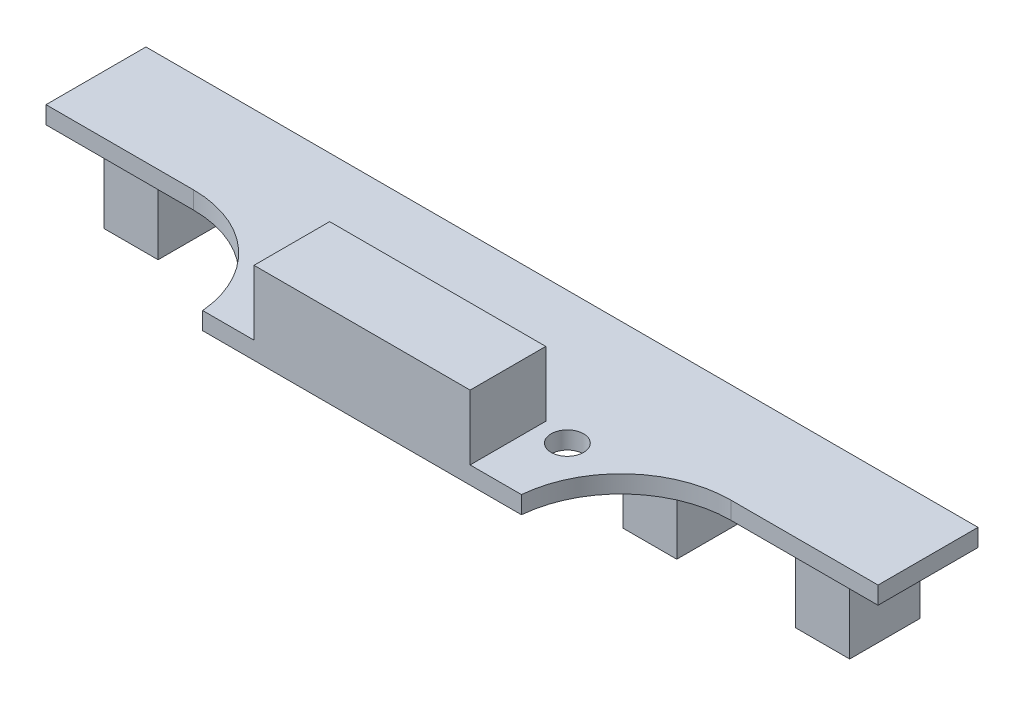
SolidWorks part; units mm, degrees
ref_plane "Front Plane" through (0, 0, 0) normal (0, 0, 1) x (1, 0, 0)
ref_plane "Top Plane" through (0, 0, 0) normal (0, 1, 0) x (1, 0, 0)
ref_plane "Right Plane" through (0, 0, 0) normal (1, 0, 0) x (0, 0, -1)
sketch "Sketch1" plane through (0, 0, 0) normal (0, 1, 0) x (1, 0, 0)
  line L0 (13.5, 12.5) -> (13.5, 6)
  line L1 (-14.75, -4.625) -> (14.75, -4.625)
  line L2 (-14.75, -4.625) -> (-14.75, 4.625)
  line L3 (-14.75, 4.625) -> (14.75, 4.625)
  line L4 (14.75, -4.625) -> (14.75, 4.625)
  line L5 (-14.75, -4.625) -> (14.75, 4.625) construction
  line L6 (-14.75, 4.625) -> (14.75, -4.625) construction
  line L7 (38.5, 4.625) -> (-38.5, 4.625)
  line L8 (38.5, 4.625) -> (38.5, 13.875)
  line L9 (38.5, 13.875) -> (-38.5, 13.875)
  line L10 (-38.5, 4.625) -> (-38.5, 13.875)
  line L11 (-2.5, 12.5) -> (2.5, 12.5)
  line L12 (-2.5, 12.5) -> (-2.5, 6)
  line L13 (-2.5, 6) -> (2.5, 6)
  line L14 (2.5, 12.5) -> (2.5, 6)
  line L15 (-2.5, 12.5) -> (2.5, 6) construction
  line L16 (-2.5, 6) -> (2.5, 12.5) construction
  line L17 (13.5, 6) -> (18.5, 6)
  line L18 (18.5, 12.5) -> (18.5, 6)
  line L19 (13.5, 12.5) -> (18.5, 12.5)
  line L20 (29.5, 12.5) -> (29.5, 6)
  line L21 (29.5, 6) -> (34.5, 6)
  line L22 (34.5, 12.5) -> (34.5, 6)
  line L23 (29.5, 12.5) -> (34.5, 12.5)
  line L24 (-2.5, 12.5) -> (13.5, 12.5) construction
  line L25 (-18.5, 12.5) -> (-18.5, 6)
  line L26 (-18.5, 12.5) -> (-13.5, 12.5)
  line L27 (-13.5, 12.5) -> (-13.5, 6)
  line L28 (-18.5, 6) -> (-13.5, 6)
  line L29 (-34.5, 12.5) -> (-34.5, 6)
  line L30 (-34.5, 12.5) -> (-29.5, 12.5)
  line L31 (-29.5, 12.5) -> (-29.5, 6)
  line L32 (-34.5, 6) -> (-29.5, 6)
  point P0 (0, 0)
  point P10 (0, 9.25)
  point P11 (0, 13.875)
  point P17 (-38.5, 9.25)
  dimension "D1" = 29.5
  dimension "D2" = 77
  dimension "D3" = 9.25
  dimension "D4" = 18.5
  dimension "D5" = 6.5
  dimension "D6" = 5
  dimension "D8" = 16
  dimension "D10" = 11
  dimension "D7" = 3
  dimension "D9" = 3
extrude "Boss-Extrude1" add sketch "Sketch1" along normal blind 1.62 contours L10 L7 L3 L8 L9 L32 L29 L30 L31 L28 L25 L26 L27 L11 L14 L13 L12 L0 L19 L18 L17 L20 L23 L22 L21 | L29 L32 L31 L30 | L25 L28 L27 L26 | L1 L4 L3 L2 | L14 L11 L12 L13 | L19 L0 L17 L18 | L23 L20 L21 L22 region at (16, 0, -9.25) region at (0, 0, 0) region at (-26.625, 0, -5.4005) region at (0, 0, -9.25) region at (32, 0, -9.25) region at (-16, 0, -9.25) region at (-32, 0, -9.25)
fillet "Fillet1" radius 10.16 2 edges at (-14.75, 0.81, -4.625) (14.75, 0.81, -4.625)
extrude "Boss-Extrude2" add sketch "Sketch1<3>" against normal blind 7 contours L23 L20 L21 L22 | L19 L0 L17 L18 | L14 L11 L12 L13 | L25 L28 L27 L26 | L29 L32 L31 L30 region at (16, 0, -9.25) region at (0, 0, -9.25) region at (32, 0, -9.25) region at (-16, 0, -9.25) region at (-32, 0, -9.25)
sketch "Sketch1<3>" plane through (0, 0, 0) normal (0, 1, 0) x (1, 0, 0) same geometry as "Sketch1"
sketch "Sketch2" plane through (0, 1.62, 0) normal (0, 1, 0) x (1, 0, 0)
  line L0 (0, -4.625) -> (0, 13.875) construction
  line L1 (-14.75, -4.625) -> (14.75, -4.625) construction
  line L2 (38.5, 13.875) -> (-38.5, 13.875) construction
  circle A0 centre (-12.75, 1.625) radius 1.5
  circle A1 centre (12.75, 1.625) radius 1.5
  point P10 (0, -4.625)
  point P11 (-12.2657, 1.625)
  dimension "D1" = 3
  dimension "D2" = 6.25
  dimension "D3" = 25.5
extrude "Cut-Extrude1" cut sketch "Sketch2" against normal up to surface (1.62 mm away) up to face at (-32, 0, -9.25)
sketch "Sketch3" plane through (0, 1.62, 0) normal (0, 1, 0) x (1, 0, 0)
  line L0 (-14.75, -4.625) -> (14.75, -4.625) construction
  line L1 (-10, -4.625) -> (10, -4.625)
  line L2 (-10, -4.625) -> (-10, 2.375)
  line L3 (-10, 2.375) -> (10, 2.375)
  line L4 (10, -4.625) -> (10, 2.375)
  point P6 (0, 2.375)
  dimension "D1" = 20
  dimension "D2" = 7
extrude "Boss-Extrude3" add sketch "Sketch3" along normal blind 6
equation "\"D2@Sketch2\"=4.75mm+\"D1@Sketch2\"/2"
equation "\"D3@Sketch2\"=22.5mm+\"D1@Sketch2\""
